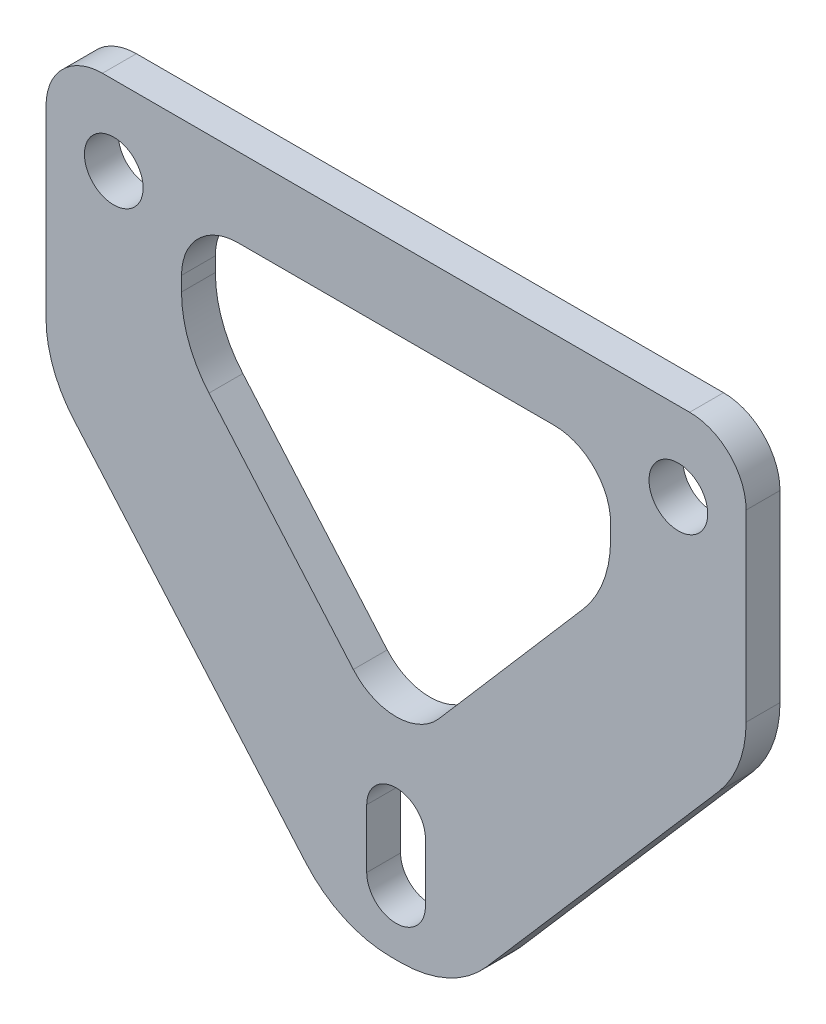
SolidWorks part; units mm, degrees
material "AISI 4130 Steel, annealed at 865C"
ref_plane "Front Plane" through (0, 0, 0) normal (0, 0, 1) x (1, 0, 0)
ref_plane "Top Plane" through (0, 0, 0) normal (0, 1, 0) x (1, 0, 0)
ref_plane "Right Plane" through (0, 0, 0) normal (1, 0, 0) x (0, 0, -1)
sketch "Sketch1" plane through (0, 0, 0) normal (0, 0, 1) x (1, 0, 0)
  line L0 (0, 3.5) -> (0, -55.5594) construction
  line L1 (-31, -0.5594) -> (31, -0.5594)
  line L2 (31, -0.5594) -> (31, -25.5594)
  line L3 (31, -25.5594) -> (5, -55.5594)
  line L4 (5, -55.5594) -> (-5, -55.5594)
  line L5 (-5, -55.5594) -> (-31, -25.5594)
  line L6 (-31, -25.5594) -> (-31, -0.5594)
  line L7 (0, -50.1594) -> (0, -44.9594) construction
  line L8 (-2.6, -50.1594) -> (-2.6, -44.9594)
  line L9 (2.6, -50.1594) -> (2.6, -44.9594)
  line L10 (25, -7.5594) -> (-25, -7.5594) construction
  line L14 (0, -39.5594) -> (19, -17.5594)
  line L18 (19, -17.5594) -> (19, -7.5594)
  line L19 (19, -7.5594) -> (-19, -7.5594)
  line L20 (-19, -7.5594) -> (-19, -17.5594)
  line L21 (-19, -17.5594) -> (0, -39.5594)
  circle A0 centre (25, -7.5594) radius 2.6
  circle A1 centre (-25, -7.5594) radius 2.6
  circle A2 centre (0, -47.5594) radius 2.6 construction
  arc A3 (-2.6, -50.1594) -> (2.6, -50.1594) centre (0, -50.1594) ccw
  arc A4 (2.6, -44.9594) -> (-2.6, -44.9594) centre (0, -44.9594) ccw
  point P17 (0, -47.5594)
  dimension "D4" = 50
  dimension "D6" = 5.2
  dimension "D8" = 7
  dimension "D9" = 38
  dimension "D1" = 62
  dimension "D2" = 25
  dimension "D3" = 10
  dimension "D5" = 40
  dimension "D7" = 55
  dimension "D10" = 10
  dimension "D11" = 32
base flange "Base-Flange1" sketch "Sketch1" thickness 3 reverse thickness direction no parameters "D1"=5
fillet "fillet 10 mm" radius 10 6 edges at (19, -17.5594, -1.5) (31, -25.5594, -1.5) (5, -55.5594, -1.5) (-5, -55.5594, -1.5) (-31, -25.5594, -1.5) (-19, -17.5594, -1.5)
fillet "fillet 5 mm" radius 5 5 edges at (19, -7.5594, -1.5) (31, -0.5594, -1.5) (-19, -7.5594, -1.5) (-31, -0.5594, -1.5) (0, -39.5594, -1.5)
sketch "Bend-Lines1" [suppressed] plane through (0, 0, 0) normal (0, 1, 0) x (1, 0, 0)
sketch "Bounding-Box1" [suppressed] plane through (0, 0, 0) normal (0, 1, 0) x (1, 0, 0)
sheet metal parameters "Sheet-Metal1" thickness 3 parameters "D1"=5
flat pattern "Flat-Pattern1" [suppressed]
sketch "Bend-Lines2" plane through (0, 0, 0) normal (0, 1, 0) x (1, 0, 0)
sketch3d "Bounding-Box2" [suppressed]
  line L0 (-31, -55.5594, 0) -> (31, -55.5594, 0) construction
  line L1 (-31, -0.5594, 0) -> (31, -0.5594, 0) construction
  line L2 (-31, -55.5594, 0) -> (-31, -0.5594, 0) construction
  line L3 (31, -55.5594, 0) -> (31, -0.5594, 0) construction
